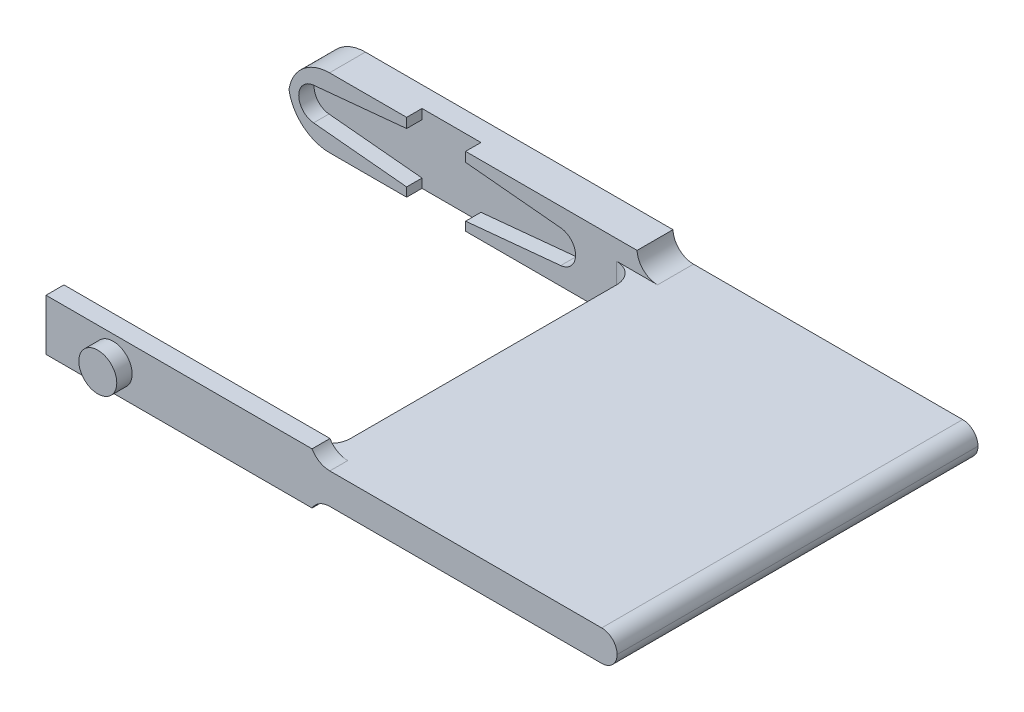
SolidWorks part; units mm, degrees
note: The reader was unsure of these and kept them because the rebuilt part matched: shared geometry of "Sketch1<16>", "Sketch1<17>", "Sketch1<18>".
ref_plane "Front Plane" through (0, 0, 0) normal (0, 0, 1) x (1, 0, 0)
ref_plane "Top Plane" through (0, 0, 0) normal (0, 1, 0) x (1, 0, 0)
ref_plane "Right Plane" through (0, 0, 0) normal (1, 0, 0) x (0, 0, -1)
sketch "Sketch1" plane through (0, 0, 0) normal (0, 0, 1) x (1, 0, 0)
  line L0 (0, 3.3371) -> (-13.5, 3.3371) construction
  line L1 (0, 3.3371) -> (0, 6.0871) construction
  line L2 (-12.0529, 4.9297) -> (0, 6.0871)
  line L3 (-13.5, 3.3371) -> (-13.5, 1.0762) construction
  line L4 (-12.0529, 1.7444) -> (0, 0.5871)
  line L5 (12.0529, 1.7444) -> (0, 0.5871)
  line L6 (12.0529, 4.9297) -> (0, 6.0871)
  line L7 (-2.75, 3.3371) -> (-2.75, -5.6277) construction
  line L8 (-14.5, 0) -> (14.5, 0)
  line L9 (-14.5, 0) -> (-14.5, 6.75)
  line L10 (-14.5, 6.75) -> (14.5, 6.75)
  line L12 (13.5, 3.3371) -> (13.5, 0.9067) construction
  line L13 (14.5, 4.8371) -> (49.25, 4.8371)
  line L14 (14.5, 4.8371) -> (14.5, 1.9129) construction
  line L15 (14.5, 1.8371) -> (49.25, 1.8371)
  line L16 (49.25, 4.8371) -> (49.25, 1.8371)
  line L17 (14.5, 0) -> (19.5, 0)
  line L18 (14.5, 6.75) -> (14.5, 0)
  line L19 (14.5, 0) -> (14.5, 6.75)
  line L20 (14.5, 6.75) -> (19.5, 6.75)
  line L21 (19.5, 0) -> (19.5, 6.75)
  circle A0 centre (0, 3.3371) radius 2.75 construction
  arc A1 (-12.0529, 4.9297) -> (-12.0529, 1.7444) centre (-11.9, 3.3371) ccw
  arc A2 (12.0529, 4.9297) -> (12.0529, 1.7444) centre (11.9, 3.3371) cw
  circle A3 centre (-11.9, 3.3371) radius 0.2914
  circle A4 centre (-9.8632, 3.3371) radius 0.2914
  circle A5 centre (-7.8264, 3.3371) radius 0.2914
  circle A6 centre (7.8264, 3.3371) radius 0.2914
  circle A7 centre (9.8632, 3.3371) radius 0.2914
  circle A8 centre (11.9, 3.3371) radius 0.2914
  point P2 (-14.5, 3.375)
  point P27 (0, 6.75)
  point P34 (14.25, 3.3371)
  point P35 (49.25, 3.3371)
  dimension "D1" = 5.5
  dimension "D9" = 1.6
  dimension "D3" = 3
  dimension "D5" = 29
  dimension "D7" = 6.75
  dimension "D8" = 1.7444
  dimension "D11" = 27
  dimension "D6" = 13.5
  dimension "D4" = 34.75
  dimension "D10" = 34
  dimension "D2" = 3
extrude "Boss-Extrude10" add sketch "Sketch1" along normal blind 3.5
extrude "Boss-Extrude15" add sketch "Sketch1<16>" along normal offset from surface (2 mm away) 1.5 contours A7 | A8 | A4 | A5 | A3 | L2 A1 L4 A0 A5 A4 A3 | L2 A0 L4 L5 L6 | A2 L6 A0 L5 A7 A6 A8 | A6 up to face at (0, 3.375, 3.5)
sketch "Sketch1<16>" plane through (0, 0, 0) normal (0, 0, 1) x (1, 0, 0) same geometry as "Sketch1"
ref_plane "Ground Plane" through (0, 0, 35.2) normal (0, 0, 1) x (1, 0, 0)
extrude "Boss-Extrude17" add sketch "Sketch1<17>" along direction (0, 0, 1) on the side of the normal up to surface (35.2 mm away) contours L13 L18 L15 L16 up to plane "Ground Plane"
sketch "Sketch1<17>" plane through (0, 0, 0) normal (0, 0, 1) x (1, 0, 0) same geometry as "Sketch1"
extrude "Boss-Extrude20" add sketch "Sketch1<18>" along normal up to surface (3.5 mm away) contours L13 L21 L20 L18 | L15 L21 L13 L18 | L17 L21 L15 L18 up to face at (0, 3.375, 3.5)
sketch "Sketch1<18>" plane through (0, 0, 0) normal (0, 0, 1) x (1, 0, 0) same geometry as "Sketch1"
sketch "Sketch2" plane through (0, 0, 35.2) normal (0, 0, 1) x (1, 0, 0)
  line L0 (14.7, 3.3371) -> (-6.45, 3.3371) construction
  line L1 (19.5, 1.8371) -> (19.5, 4.8371) construction
  line L2 (-6.45, 0.8371) -> (19.5, 0.8371)
  line L3 (-6.45, 5.8371) -> (19.5, 5.8371)
  line L4 (-6.45, 5.8371) -> (-6.45, 0.8371)
  line L5 (19.5, 5.8371) -> (19.5, 0.8371)
  point P6 (19.5, 3.3371)
  point P7 (19.5, 3.3371)
  dimension "D1" = 5
  dimension "D3" = 6.45
extrude "Boss-Extrude18" add sketch "Sketch2" against normal blind 1.75
fillet "Fillet1" radius 2 4 edges at (19.5, 4.8371, 34.325) (19.5, 4.8371, 1.75) (19.5, 1.8371, 34.325) (19.5, 1.8371, 1.75)
fillet "Fillet3" radius 2 2 edges at (19.5, 3.3371, 33.45) (19.5, 3.3371, 3.5)
fillet "Fillet2" radius 4 2 edges at (-14.5, 6.75, 1.75) (-14.5, 0, 1.75)
sketch "Sketch3" plane through (0, 0, 3.5) normal (0, 0, 1) x (1, 0, 0)
  line L0 (-0.1021, 0) -> (-0.1021, 6.75) construction
  line L1 (-2.9771, 6.75) -> (-2.9771, 0) construction
  line L3 (-10.5, 6.75) -> (19.5, 6.75) construction
  line L4 (-14.4509, 3.375) -> (-0.1021, 3.375) construction
  line L5 (2.7729, 6.75) -> (2.7729, 0) construction
  line L6 (2.7729, 6.75) -> (2.7729, 5.625)
  line L7 (-2.9771, 5.625) -> (2.7729, 5.625)
  line L8 (-2.9771, 0) -> (2.7729, 0)
  line L9 (-2.9771, 0) -> (-2.9771, 1.125)
  line L10 (-2.9771, 1.125) -> (2.7729, 1.125)
  line L11 (2.7729, 0) -> (2.7729, 1.125)
  line L12 (-2.9771, 6.75) -> (2.7729, 6.75)
  line L13 (-2.9771, 6.75) -> (-2.9771, 5.625)
  line L19 (-10.5, 0) -> (19.5, 0) construction
  circle A0 centre (-0.1021, 3.375) radius 2.875 construction
  circle A1 centre (-0.1021, 3.375) radius 2.875 construction
  circle A2 centre (-0.1021, 3.375) radius 2.25 construction
  circle A3 centre (-0.1021, 3.375) radius 2.25 construction
extrude "Cut-Extrude1" cut sketch "Sketch3" against normal up to surface (1.5 mm away)
sketch "Sketch4" plane through (0, 0, 35.2) normal (0, 0, 1) x (1, 0, 0)
  circle A0 centre (0.1021, 3.375) radius 1.85
  circle A1 centre (0.1021, 3.375) radius 2.25 construction
  circle A7 centre (0.1021, 3.375) radius 2.25
  dimension "D1" = 3.7
extrude "Boss-Extrude19" add sketch "Sketch4" along normal blind 1.5 contours A0
fillet "Fillet4" radius 1.5 2 edges at (49.25, 4.8371, 17.6) (49.25, 1.8371, 17.6)
equation "\"D5@Sketch1\"=\"D6@Sketch1\"*2+2"
